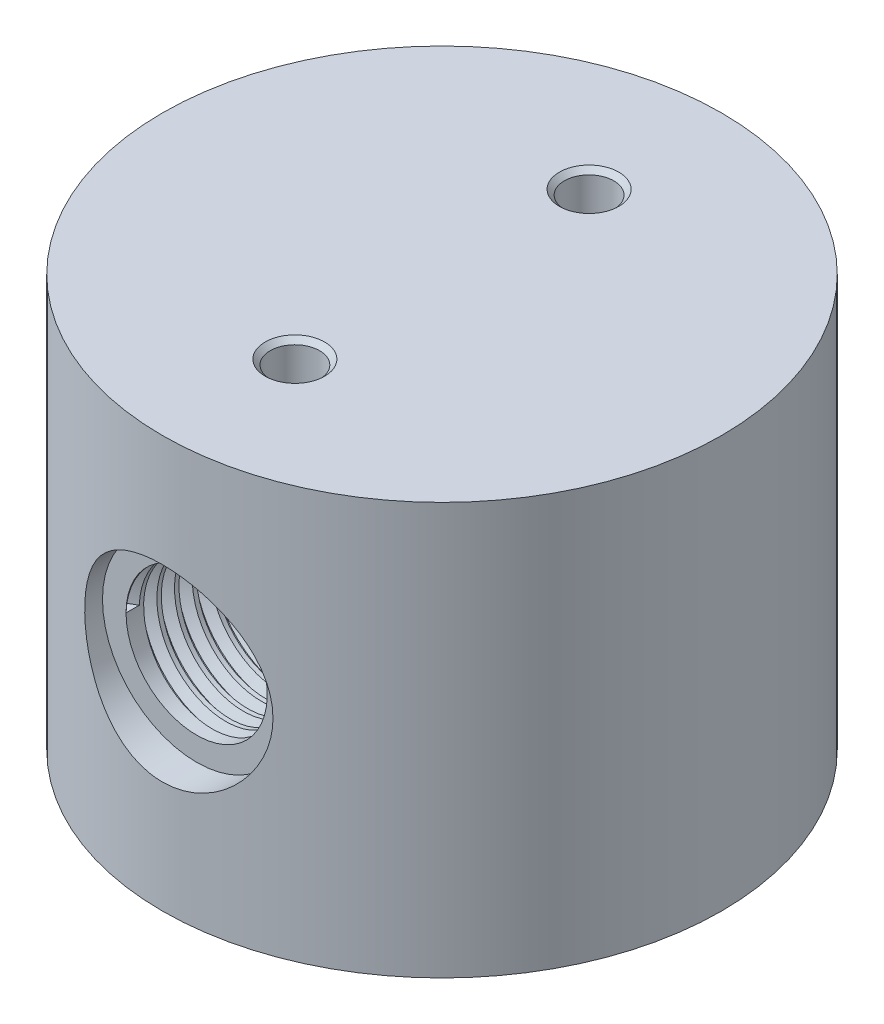
SolidWorks part; units mm, degrees
material "AISI 1020"
ref_plane "Plano superior" through (0, 0, 0) normal (0, 0, 1) x (1, 0, 0)
ref_plane "Plano frontal" through (0, 0, 0) normal (0, 1, 0) x (1, 0, 0)
ref_plane "Plano direito" through (0, 0, 0) normal (1, 0, 0) x (0, 0, -1)
sketch "Esboço1" plane through (0, 0, 0) normal (0, 1, 0) x (1, 0, 0)
  circle A0 centre (0, 0) radius 23.75
  dimension "D1" = 47.5
extrude "Ressalto-extrusão1" add sketch "Esboço1" along normal blind 35
sketch "Esboço3" plane through (0, 0, 0) normal (1, 0, 0) x (0, 0, -1)
  line L0 (-23.75, 17.5) -> (23.75, 17.5)
  line L2 (-23.85, 25.5) -> (-20.85, 25.5)
  line L3 (-20.85, 25.5) -> (-20.85, 23.5)
  line L4 (-20.85, 23.5) -> (23.75, 23.5)
  line L5 (23.75, 0) -> (23.75, 35) construction
  line L6 (-23.85, 25.5) -> (-23.75, 17.5)
  line L7 (-23.75, 35) -> (-23.75, 0) construction
  line L9 (23.75, 17.5) -> (23.75, 23.5)
  line L10 (23.75, 35) -> (-23.75, 35) construction
  dimension "D1" = 47.5
  dimension "D2" = 3
  dimension "D3" = 44.6
  dimension "D4" = 8
  dimension "D5" = 2
  dimension "D6" = 9.5
revolve "Corte-Revolução1" cut sketch "Esboço3" angle 360 about L0
cosmetic thread "Representação de rosca1"
thread "Rosca1" pitch 1.5 method cut profile "Perfil da rosca2" start angle 0, offset 0, length 0, pitch 1.5, diameter 12
ref_plane "Plano2" through (-6, 17.5, 20.85) normal (0, -1, 0) x (-1, 0, 0)
sketch "Perfil da rosca2" plane through (-6, 17.5, 20.85) normal (0, -1, 0) x (-1, 0, 0)
  line L0 (0, 0) -> (0, 1.5) construction
  line L1 (0, 0) -> (0.8119, 0.4687)
  line L2 (0.8119, 0.4687) -> (0.8119, 0.6562)
  line L3 (0.8119, 0.6562) -> (0, 1.125)
  line L4 (0.8119, 0.5625) -> (0, 0.5625) construction
  line L11 (0, 0) -> (0, 1.125)
  point P2 (0, 0)
  dimension "Pitch" = 1.5
  dimension "Profile_Angle" = 60
  dimension "Profile_Land" = 0.1875
  dimension "Profile_Height" = 0.8119
hole_wizard "Furo roscado de M51" positions "Esboço13" profile "Esboço14" tap size "M5" standard "DIN"
sketch "Esboço13" plane through (0, 35, 0) normal (0, 1, 0) x (1, 0, 0)
  point P0 (0, 12.5)
  point P2 (0, -12.5)
  dimension "D1" = 25
  dimension "D2" = 12.5
cosmetic thread "Rosca de furo1"
cosmetic thread "Rosca de furo2"
sketch "Esboço14" plane through (0, 35, -12.5) normal (1, 0, 0) x (0, 0, 1)
  line L0 (0, 0) -> (0, 10.2618)
  line L1 (0, 10.2618) -> (2.1, 9)
  line L2 (2.1, 9) -> (2.1, 0.425)
  line L3 (2.1, 0.425) -> (2.525, 0)
  line L5 (2.525, 0) -> (0, 0)
  line L6 (-2.1, 0.425) -> (-2.525, 0) construction
  line L10 (0, 10.2618) -> (-2.1, 9) construction
  line L11 (0, -6.35) -> (0, 107.95) construction
  dimension "Tap Drill Dia." = 4.2
  dimension "Tap Drill Depth" = 9
  dimension "Near C'Sink Dia." = 5.05
  dimension "Near C'Sink Angle" = 90
  dimension "Drill Angle" = 118
